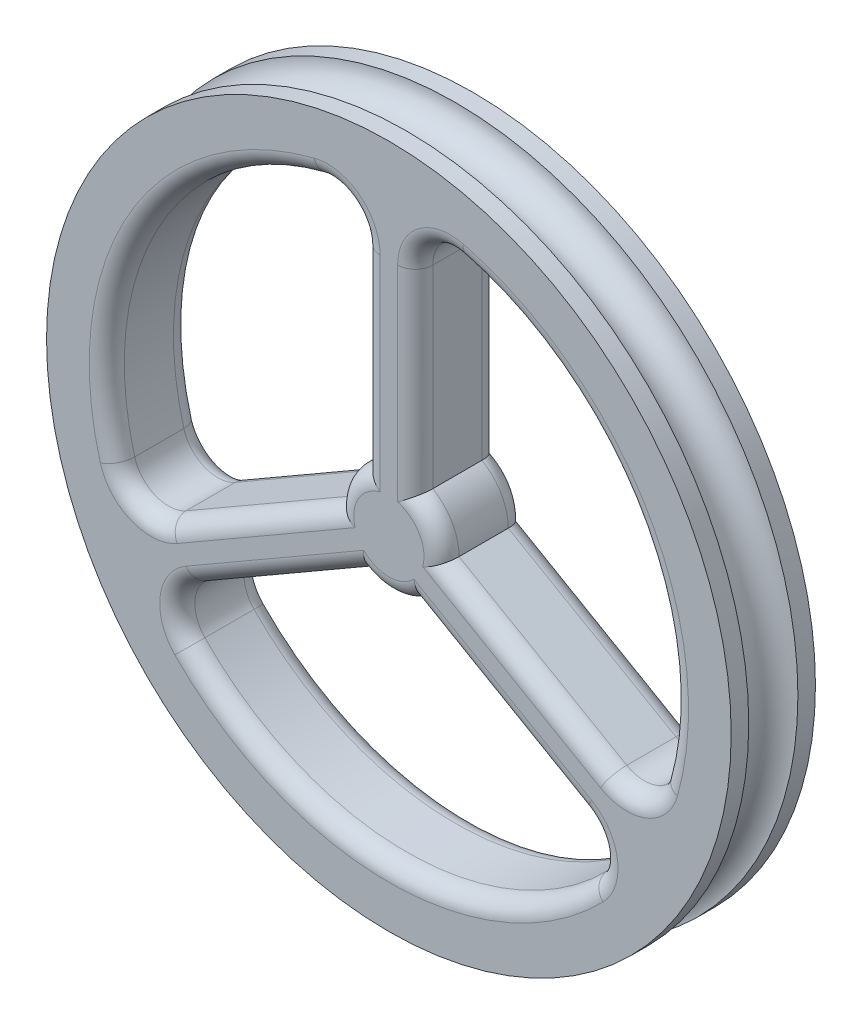
SolidWorks part; units mm, degrees
ref_plane "Front Plane" through (0, 0, 0) normal (0, 0, 1) x (1, 0, 0)
ref_plane "Top Plane" through (0, 0, 0) normal (0, 1, 0) x (1, 0, 0)
ref_plane "Right Plane" through (0, 0, 0) normal (1, 0, 0) x (0, 0, -1)
sketch "Sketch1" plane through (0, 0, 0) normal (0, 0, 1) x (1, 0, 0)
  circle A0 centre (0, 0) radius 24.765
  dimension "D1" = 49.53
extrude "Boss-Extrude1" add sketch "Sketch1" along normal blind 6.096
sketch "Sketch3" plane through (0, 0, 0) normal (1, 0, 0) x (0, 0, -1)
  line L0 (0, 24.765) -> (-6.096, 24.765) construction
  circle A0 centre (-3.048, 24.765) radius 1.778
  dimension "D1" = 3.556
ref_axis "Axis1" through (0, 0, 6.096) along (0, 0, -1)
revolve "Cut-Revolve1" cut sketch "Sketch3" angle 360 about axis through (0, 0, 6.096) along (0, 0, -1)
sketch "Sketch6" plane through (0, 0, 0) normal (0, 0, -1) x (-1, 0, 0)
  line L0 (-1.25, 0.6305) -> (1.25, 0.6305)
  line L1 (0, 0) -> (0, 30.183) construction
  line L2 (1.905, 3.2996) -> (1.905, 20.32)
  line L3 (3.81, 0) -> (18.5501, -8.5102)
  line L4 (-1.905, 3.2996) -> (-1.905, 20.32)
  line L5 (0, 0) -> (26.1392, -15.0915) construction
  line L6 (1.905, -3.2996) -> (16.6451, -11.8098)
  line L7 (-1.905, -3.2996) -> (-16.6451, -11.8098)
  line L8 (0, 0) -> (-26.1392, -15.0915) construction
  line L9 (-3.81, 0) -> (-18.5501, -8.5102)
  arc A0 (-1.25, 0.6305) -> (1.25, 0.6305) centre (0, 0) ccw
  circle A1 centre (0, 0) radius 3.81
  circle A2 centre (0, 0) radius 20.4091
  point P9 (0, 0)
  point P24 (0, 0)
  dimension "D1" = 2.5
  dimension "D2" = 1.4
  dimension "D5" = 7.62
  dimension "D3" = 1.905
  dimension "D4" = 20.32
  dimension "D6" = 3
extrude "Cut-Extrude1" cut sketch "Sketch6" against normal up to next contours L4 A2 L9 A1 | L3 A2 L2 A1 | L7 A2 L6 A1 region at (-10.7648, 6.2151, 0) region at (10.7648, 6.2151, 0) region at (0, -12.4301, 0)
fillet "Fillet1" radius 2.54 6 edges at (-18.5501, -8.5102, 3.048) (-16.6451, -11.8098, 3.048) (16.6451, -11.8098, 3.048) (18.5501, -8.5102, 3.048) (-1.905, 20.32, 3.048) (1.905, 20.32, 3.048)
extrude "Cut-Extrude2" cut sketch "Sketch6<4>" against normal offset from surface (5.588 mm away) 0.508 contours L0 A0 region at (0, -0.2723, 0) up to face at (0, -10.3565, 6.096)
sketch "Sketch6<4>" plane through (0, 0, 0) normal (0, 0, -1) x (-1, 0, 0) same geometry as "Sketch6"
fillet "Fillet2" radius 1.27 36 edges at (-15.2827, -12.1586, 0) (-7.9706, -6.8015, 0) (0, -3.81, 0) (7.9706, -6.8015, 0) (15.2827, -12.1586, 0) (0, -20.4091, 0) (-2.8883, 19.3145, 0) (-1.905, 10.3035, 0) (-3.2996, 1.905, 0) (-9.8756, -3.502, 0) (-18.171, -7.1559, 0) (-17.6748, 10.2046, 0) (18.171, -7.1559, 0) (9.8756, -3.502, 0) (3.2996, 1.905, 0) (1.905, 10.3035, 0) (2.8883, 19.3145, 0) (17.6748, 10.2046, 0) (0, -3.81, 6.096) (-7.9706, -6.8015, 6.096) (-15.2827, -12.1586, 6.096) (0, -20.4091, 6.096) (15.2827, -12.1586, 6.096) (7.9706, -6.8015, 6.096) (-3.2996, 1.905, 6.096) (-1.905, 10.3035, 6.096) (-2.8883, 19.3145, 6.096) (-17.6748, 10.2046, 6.096) (-18.171, -7.1559, 6.096) (-9.8756, -3.502, 6.096) (3.2996, 1.905, 6.096) (9.8756, -3.502, 6.096) (18.171, -7.1559, 6.096) (17.6748, 10.2046, 6.096) (2.8883, 19.3145, 6.096) (1.905, 10.3035, 6.096)
chamfer "Chamfer1" distance 0.635 angle 45 2 edges at (0, 0.6305, 0) (0, -1.4, 0)
equation "\"0.05n\"=0.1"
